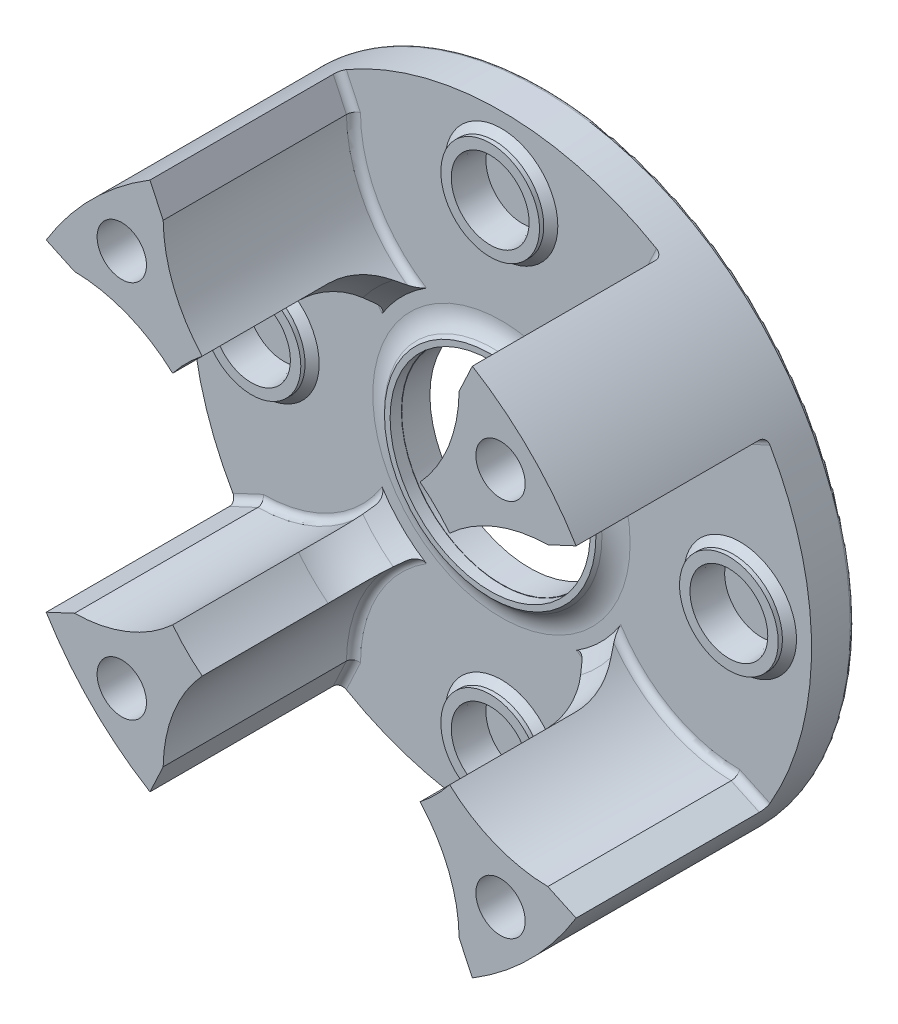
SolidWorks part; units mm, degrees
ref_plane "Front Plane" through (0, 0, 0) normal (0, 0, 1) x (1, 0, 0)
ref_plane "Top Plane" through (0, 0, 0) normal (0, 1, 0) x (1, 0, 0)
ref_plane "Right Plane" through (0, 0, 0) normal (1, 0, 0) x (0, 0, -1)
sketch "Sketch1" plane through (0, 0, 0) normal (0, 0, 1) x (1, 0, 0)
  circle A0 centre (0, 0) radius 7.075
  circle A1 centre (0, 0) radius 22
  circle A2 centre (0, 16.933) radius 2.6
  circle A3 centre (16.933, 0) radius 2.6
  circle A4 centre (0, -16.933) radius 2.6
  circle A5 centre (-16.933, 0) radius 2.6
  point P15 (0, 0)
  dimension "D1" = 14.15
  dimension "D2" = 44
  dimension "D3" = 5.2
  dimension "D4" = 16.933
  dimension "D5" = 4
extrude "Boss-Extrude1" add sketch "Sketch1" along normal blind 3
sketch "Sketch2" plane through (0, 0, 0) normal (0, 0, -1) x (-1, 0, 0)
  circle A0 centre (0, 0) radius 10.85
  dimension "D1" = 21.7
extrude "Cut-Extrude1" cut sketch "Sketch2" against normal blind 1
sketch "Sketch4" plane through (0, 0, 0) normal (0, 0, -1) x (-1, 0, 0)
  circle A0 centre (0, 0) radius 13.4857
  circle A1 centre (0, 0) radius 20.6054
extrude "Boss-Extrude3" add sketch "Sketch4" against normal blind 1.5
sketch "Sketch6" plane through (0, 0, 3) normal (0, 0, 1) x (1, 0, 0)
  circle A0 centre (0, 16.933) radius 2.6
  circle A1 centre (0, 16.933) radius 3.5
  circle A2 centre (16.933, 0) radius 2.6
  circle A3 centre (16.933, 0) radius 3.5
  circle A4 centre (0, -16.933) radius 2.6
  circle A5 centre (0, -16.933) radius 3.5
  circle A6 centre (-16.933, 0) radius 2.6
  circle A7 centre (-16.933, 0) radius 3.5
  circle A8 centre (0, 16.933) radius 2.6 construction
  point P16 (0, 0)
  dimension "D1" = 7
  dimension "D2" = 4
extrude "Boss-Extrude4" add sketch "Sketch6" along normal blind 0.8
fillet "Fillet1" radius 0.25 1 edges at (22, 0, 0)
sketch "Sketch7" plane through (0, 0, 3) normal (0, 0, 1) x (1, 0, 0)
  line L0 (0, 0) -> (-5.0028, 5.0028)
  line L1 (-5.0028, 5.0028) -> (-11.4343, 18.7951)
  line L2 (-5.0028, 5.0028) -> (-18.7951, 11.4343)
  line L3 (5.0028, 5.0028) -> (11.4343, 18.7951)
  line L4 (5.0028, 5.0028) -> (18.7951, 11.4343)
  line L5 (5.0028, -5.0028) -> (18.7951, -11.4343)
  line L6 (5.0028, -5.0028) -> (11.4343, -18.7951)
  line L7 (-5.0028, -5.0028) -> (-11.4343, -18.7951)
  line L8 (-5.0028, -5.0028) -> (-18.7951, -11.4343)
  circle A0 centre (0, 0) radius 7.075 construction
  circle A1 centre (0, 0) radius 22 construction
  arc A2 (-18.7951, 11.4343) -> (-11.4343, 18.7951) centre (0, 0) cw
  arc A3 (11.4343, 18.7951) -> (18.7951, 11.4343) centre (0, 0) cw
  arc A4 (18.7951, -11.4343) -> (11.4343, -18.7951) centre (0, 0) cw
  arc A5 (-11.4343, -18.7951) -> (-18.7951, -11.4343) centre (0, 0) cw
  circle A6 centre (0, 0) radius 12.5
  point P22 (0, 0)
  dimension "D4" = 25
  dimension "D1" = 160
  dimension "D2" = 160
  dimension "D3" = 4
extrude "Boss-Extrude5" add sketch "Sketch7" along normal blind 13.5 contours A6 L1 L2 | A6 L8 L7 | A6 L6 L5 | A6 L4 L3 region at (-12.618, 12.618, 3) region at (12.618, 12.618, 3) region at (-12.618, -12.618, 3) region at (12.618, -12.618, 3)
sketch "Sketch8" plane through (0, 0, 16.5) normal (0, 0, 1) x (1, 0, 0)
  circle A0 centre (0, 16.933) radius 10.5
  circle A1 centre (16.933, 0) radius 10.5
  circle A2 centre (0, -16.933) radius 10.5
  circle A3 centre (-16.933, 0) radius 10.5
  circle A4 centre (0, 16.933) radius 3.9065
  circle A5 centre (16.933, 0) radius 3.9065
  circle A6 centre (0, -16.933) radius 3.9065
  circle A7 centre (-16.933, 0) radius 3.9065
  point P12 (0, 0)
  point P20 (0, 0)
  dimension "D1" = 21
  dimension "D2" = 4
  dimension "D3" = 4
extrude "Cut-Extrude3" cut sketch "Sketch8" against normal up to surface (13.5 mm away) up to face at (3.5, -16.933, 3)
sketch "Sketch9" plane through (0, 0, 16.5) normal (0, 0, 1) x (1, 0, 0)
  line L0 (0, 0) -> (-8.8388, 8.8388) construction
  line L1 (-8.8388, 8.8388) -> (-19.8683, 19.8683) construction
  arc A0 (-7.7281, 9.8248) -> (-9.8248, 7.7281) centre (0, 0) ccw construction
  circle A1 centre (-13.435, 13.435) radius 1.4
  circle A2 centre (13.435, 13.435) radius 1.4
  circle A3 centre (13.435, -13.435) radius 1.4
  circle A4 centre (-13.435, -13.435) radius 1.4
  point P18 (0, 0)
  dimension "D1" = 2.8
  dimension "D2" = 19
  dimension "D3" = 4
extrude "Cut-Extrude4" cut sketch "Sketch9" against normal blind 10
fillet "Fillet2" radius 0.5 16 edges at (-17.7923, -10.9666, 3) (-13.0515, -9.7562, 3) (-17.7923, 10.9666, 3) (-13.0515, 9.7562, 3) (-10.9666, 17.7923, 3) (-9.7562, 13.0515, 3) (10.9666, 17.7923, 3) (9.7562, 13.0515, 3) (17.7923, 10.9666, 3) (13.0515, 9.7562, 3) (17.7923, -10.9666, 3) (13.0515, -9.7562, 3) (10.9666, -17.7923, 3) (-10.9666, -17.7923, 3) (-9.7562, -13.0515, 3) (9.7562, -13.0515, 3)
chamfer "Chamfer1" distance 2.5 angle 45 4 edges at (8.8388, 8.8388, 3) (8.8388, -8.8388, 3) (-8.8388, -8.8388, 3) (-8.8388, 8.8388, 3)
fillet "Fillet3" radius 5 4 edges at (8.8388, 8.8388, 5.5) (-8.8388, 8.8388, 5.5) (-8.8388, -8.8388, 5.5) (8.8388, -8.8388, 5.5)
chamfer "Chamfer2" distance 0.5 angle 45 4 edges at (3.5, 16.933, 3) (20.433, 0, 3) (3.5, -16.933, 3) (-13.433, 0, 3)
sketch "Sketch10" plane through (0, 0, 3) normal (0, 0, 1) x (1, 0, 0)
  circle A0 centre (0, 0) radius 7.1
  circle A1 centre (0, 0) radius 8.5
  dimension "D1" = 17
extrude "Boss-Extrude6" add sketch "Sketch10" along normal up to surface (0.8 mm away) up to face at (-13.433, 0, 3.8)
chamfer "Chamfer3" distance 1 angle 45 1 edges at (8.5, 0, 3.8)
fillet "Fillet4" radius 2 1 edges at (8.3, 0, 3)
chamfer "Chamfer4" distance 0.15 angle 45 4 edges at (2.6, -16.933, 3.8) (-14.333, 0, 3.8) (19.533, 0, 3.8) (2.6, 16.933, 3.8)
draft "Draft1" type of draft neutral plane draft angle 4 faces to draft 4 face at (2.6, -16.933, 3.65) face at (19.533, 0, 3.65) face at (-14.333, 0, 3.65) face at (2.6, 16.933, 3.65) neutral plane through (0, 0, 1.5) neutral plane normal (0, 0, 1) parameters "D1"=4
sketch "Sketch11" plane through (0, 0, 16.5) normal (0, 0, 1) x (1, 0, 0)
  circle A0 centre (13.435, 13.435) radius 1.75
  circle A1 centre (-13.435, 13.435) radius 1.75
  circle A2 centre (-13.435, -13.435) radius 1.75
  circle A3 centre (13.435, -13.435) radius 1.75
  dimension "D1" = 3.5
  dimension "D2" = 3.5
  dimension "D3" = 3.5
  dimension "D4" = 3.5
extrude "Cut-Extrude5" cut sketch "Sketch11" against normal blind 5
